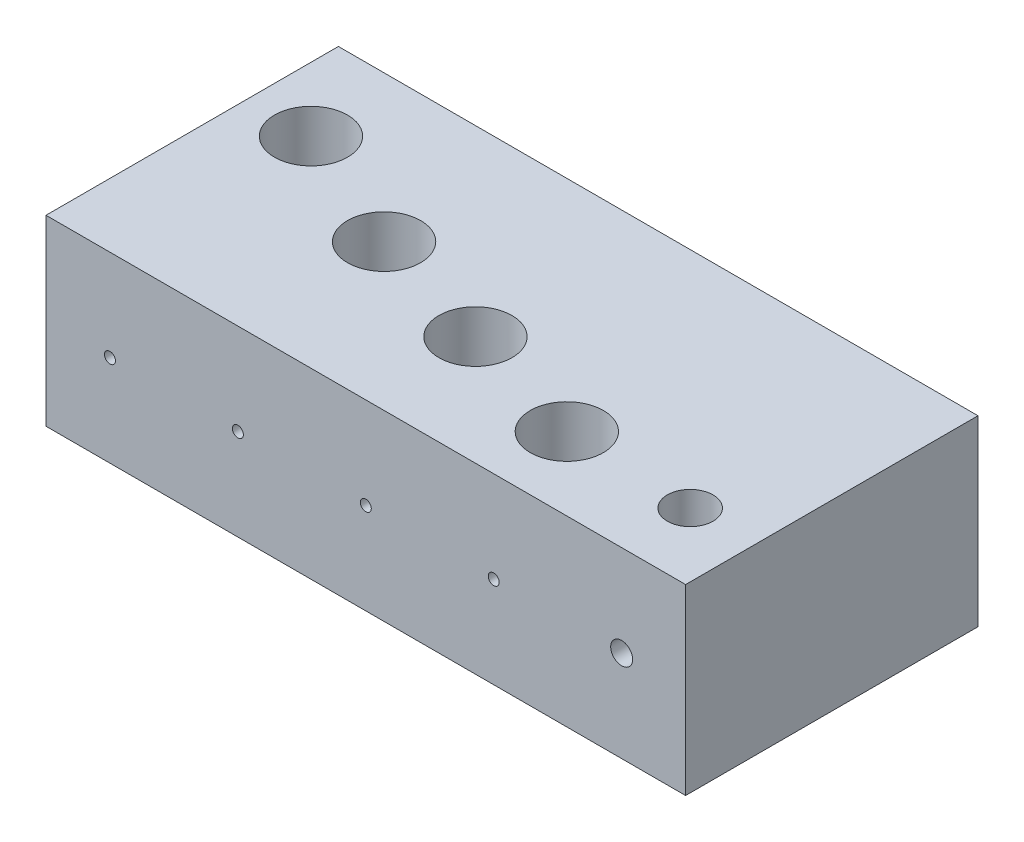
SolidWorks part; units mm, degrees
ref_plane "Front Plane" through (0, 0, 0) normal (0, 0, 1) x (1, 0, 0)
ref_plane "Top Plane" through (0, 0, 0) normal (0, 1, 0) x (1, 0, 0)
ref_plane "Right Plane" through (0, 0, 0) normal (1, 0, 0) x (0, 0, -1)
sketch "Sketch1" plane through (0, 0, 0) normal (0, 0, 1) x (1, 0, 0)
  line L1 (35, -10) -> (-35, -10)
  line L2 (35, -10) -> (35, 10)
  line L3 (35, 10) -> (-35, 10)
  line L4 (-35, -10) -> (-35, 10)
  line L5 (35, -10) -> (-35, 10) construction
  line L6 (35, 10) -> (-35, -10) construction
  point P0 (0, 0)
extrude "Boss-Extrude1" add sketch "Sketch1" along normal blind 32
sketch "Sketch3" plane through (0, 0, 32) normal (0, 0, 1) x (1, 0, 0)
  line L0 (0, 0) -> (-28, 0) construction
  line L1 (0, 0) -> (28, 0) construction
  circle A0 centre (0, 0) radius 0.6
  circle A1 centre (-14, 0) radius 0.6
  circle A2 centre (-28, 0) radius 0.6
  circle A3 centre (14, 0) radius 0.6
  circle A4 centre (28, 0) radius 1.2
extrude "Cut-Extrude1" cut sketch "Sketch3" against normal blind 10 contours A4
extrude "Cut-Extrude2" cut sketch "Sketch3<3>" against normal blind 12 contours A3
sketch "Sketch3<3>" plane through (0, 0, 32) normal (0, 0, 1) x (1, 0, 0) same geometry as "Sketch3"
extrude "Cut-Extrude3" cut sketch "Sketch3<4>" against normal blind 16 contours A0
sketch "Sketch3<4>" plane through (0, 0, 32) normal (0, 0, 1) x (1, 0, 0) same geometry as "Sketch3"
extrude "Cut-Extrude4" cut sketch "Sketch3<5>" against normal blind 20 contours A1
sketch "Sketch3<5>" plane through (0, 0, 32) normal (0, 0, 1) x (1, 0, 0) same geometry as "Sketch3"
extrude "Cut-Extrude5" cut sketch "Sketch3<6>" against normal blind 26 contours A2
sketch "Sketch3<6>" plane through (0, 0, 32) normal (0, 0, 1) x (1, 0, 0) same geometry as "Sketch3"
sketch "Sketch4" plane through (0, 10, 0) normal (0, 1, 0) x (1, 0, 0)
  line L0 (0, -32) -> (28, -32) construction
  line L1 (35, -32) -> (-35, -32) construction
  line L2 (0, -32) -> (-28, -32) construction
  line L3 (28, -32) -> (28, -24.5) construction
  line L4 (14, -32) -> (14, -24) construction
  line L5 (0, -32) -> (0, -20) construction
  line L6 (-14, -32) -> (-14, -16) construction
  line L7 (-28, -32) -> (-28, -10) construction
  circle A0 centre (28, -24.5) radius 2.5
  circle A1 centre (14, -24) radius 4
  circle A2 centre (0, -20) radius 4
  circle A3 centre (-14, -16) radius 4
  circle A4 centre (-28, -10) radius 4
extrude "Cut-Extrude6" cut sketch "Sketch4" against normal blind 15
